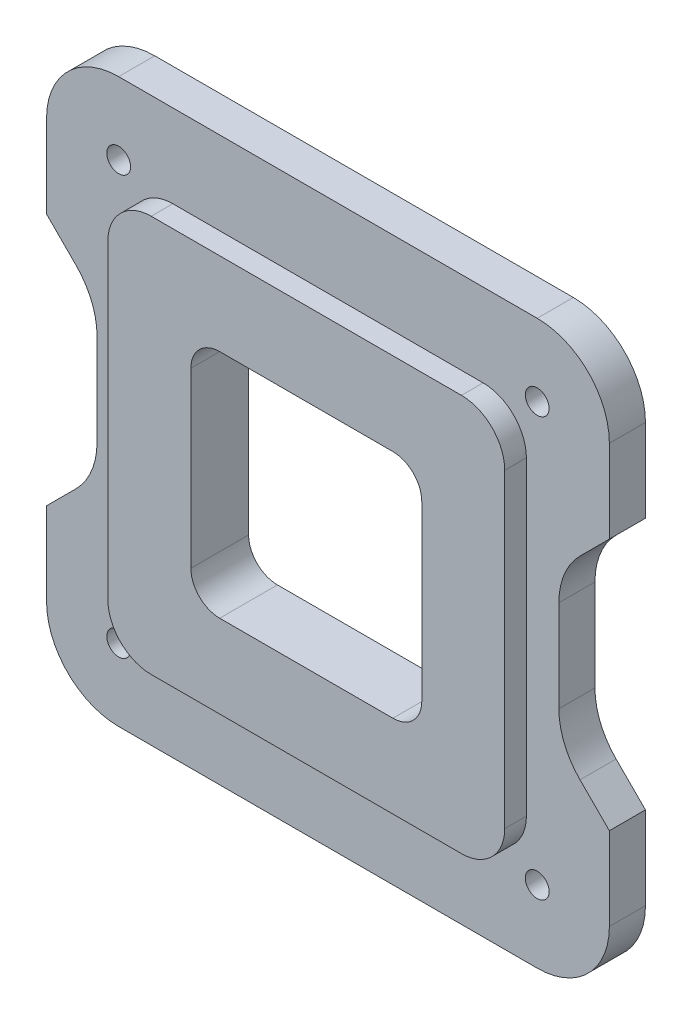
SolidWorks part; units mm, degrees
ref_plane "Front Plane" through (0, 0, 0) normal (0, 0, 1) x (1, 0, 0)
ref_plane "Top Plane" through (0, 0, 0) normal (0, 1, 0) x (1, 0, 0)
ref_plane "Right Plane" through (0, 0, 0) normal (1, 0, 0) x (0, 0, -1)
sketch "Sketch1" plane through (0, 0, 0) normal (0, 0, 1) x (1, 0, 0)
  line L0 (0, -39) -> (0, 39) construction
  line L1 (-29, 39) -> (29, 39)
  line L2 (-39, 29) -> (-39, 17.5)
  line L3 (-29, -39) -> (29, -39)
  line L4 (39, 29) -> (39, 17.5)
  line L5 (-29, -29) -> (-29, 29) construction
  line L6 (-29, 29) -> (29, 29) construction
  line L7 (-39, -17.5) -> (-34.9289, -13.4289)
  line L8 (-32, -6.3579) -> (-32, 6.3579)
  line L9 (0, 21.2748) -> (0, 0) construction
  line L10 (-87.7649, 0) -> (-84.8849, 0) construction
  line L11 (-39, 17.5) -> (-34.9289, 13.4289)
  line L12 (-39, -17.5) -> (-39, -29)
  line L13 (-39, 0) -> (-39, -17.5) construction
  line L14 (-39, 17.5) -> (-39, 0) construction
  line L15 (39, 17.5) -> (34.9289, 13.4289)
  line L16 (32, -6.3579) -> (32, 6.3579)
  line L17 (39, -17.5) -> (34.9289, -13.4289)
  line L18 (39, -17.5) -> (39, -29)
  line L19 (39, 0) -> (39, -17.5) construction
  line L20 (39, 17.5) -> (39, 0) construction
  arc A0 (-39, -29) -> (-29, -39) centre (-29, -29) ccw
  arc A1 (29, -39) -> (39, -29) centre (29, -29) ccw
  arc A2 (39, 29) -> (29, 39) centre (29, 29) ccw
  arc A3 (-29, 39) -> (-39, 29) centre (-29, 29) ccw
  circle A4 centre (-29, 29) radius 2.75 construction
  circle A5 centre (29, 29) radius 2.75 construction
  circle A6 centre (29, -29) radius 2.75 construction
  circle A7 centre (-29, -29) radius 2.75 construction
  arc A8 (34.9289, 13.4289) -> (32, 6.3579) centre (42, 6.3579) ccw
  arc A9 (32, -6.3579) -> (34.9289, -13.4289) centre (42, -6.3579) ccw
  arc A10 (-34.9289, 13.4289) -> (-32, 6.3579) centre (-42, 6.3579) cw
  arc A11 (-32, -6.3579) -> (-34.9289, -13.4289) centre (-42, -6.3579) cw
  point P32 (-32, 0)
  point P41 (32, 10.5)
  point P44 (32, -10.5)
  point P47 (-32, 10.5)
  point P50 (-32, -10.5)
  dimension "D1" = 10
  dimension "D2" = 5.5
  dimension "D7" = 10
  dimension "D3" = 58
  dimension "D4" = 135
  dimension "D5" = 32
  dimension "D6" = 35
extrude "Boss-Extrude1" add sketch "Sketch1" along normal blind 5
sketch "Sketch2" plane through (0, 0, 5) normal (0, 0, -1) x (-1, 0, 0)
  line L0 (0, 27.5) -> (0, -27.5) construction
  line L1 (-21.5, 27.5) -> (21.5, 27.5)
  line L2 (-27.5, 21.5) -> (-27.5, -21.5)
  line L3 (-21.5, -27.5) -> (21.5, -27.5)
  line L4 (27.5, 21.5) -> (27.5, -21.5)
  arc A0 (27.5, 21.5) -> (21.5, 27.5) centre (21.5, 21.5) ccw
  arc A1 (27.5, -21.5) -> (21.5, -27.5) centre (21.5, -21.5) cw
  arc A2 (-27.5, -21.5) -> (-21.5, -27.5) centre (-21.5, -21.5) ccw
  arc A3 (-27.5, 21.5) -> (-21.5, 27.5) centre (-21.5, 21.5) cw
  dimension "D1" = 6
  dimension "D2" = 55
extrude "Boss-Extrude2" add sketch "Sketch2" against normal blind 3
sketch "Sketch3" plane through (0, 0, 0) normal (0, 0, -1) x (-1, 0, 0)
  line L1 (-12, -16) -> (12, -16)
  line L2 (-16, -12) -> (-16, 12)
  line L3 (-12, 16) -> (12, 16)
  line L4 (16, -12) -> (16, 12)
  circle A0 centre (0, 0) radius 16 construction
  arc A1 (-16, -12) -> (-12, -16) centre (-12, -12) ccw
  arc A2 (12, -16) -> (16, -12) centre (12, -12) ccw
  arc A3 (16, 12) -> (12, 16) centre (12, 12) ccw
  arc A4 (-12, 16) -> (-16, 12) centre (-12, 12) ccw
  dimension "D1" = 32
  dimension "D2" = 4
extrude "Cut-Extrude1" cut sketch "Sketch3" against normal through all both and the other way through all
sketch "Sketch4" plane through (0, 0, 0) normal (0, 0, -1) x (-1, 0, 0)
  point P0 (-29, -29)
  point P3 (29, -29)
  point P6 (29, 29)
  point P9 (-29, 29)
hole_wizard "Tap Drill for M4 Tap1" positions "Sketch4" profile "Sketch5" hole size "M4" standard "DIN"
sketch "Sketch5" plane through (29, -29, 0) normal (1, 0, 0) x (0, 1, 0)
  line L0 (0, 0) -> (0, 10.9914)
  line L1 (0, 10.9914) -> (1.65, 10)
  line L2 (1.65, 10) -> (1.65, 0)
  line L5 (1.65, 0) -> (0, 0)
  line L10 (0, 10.9914) -> (-1.65, 10) construction
  line L11 (0, -6.35) -> (0, 107.95) construction
  dimension "Hole Dia." = 3.3
  dimension "Hole Depth" = 10
  dimension "Drill Angle" = 118
